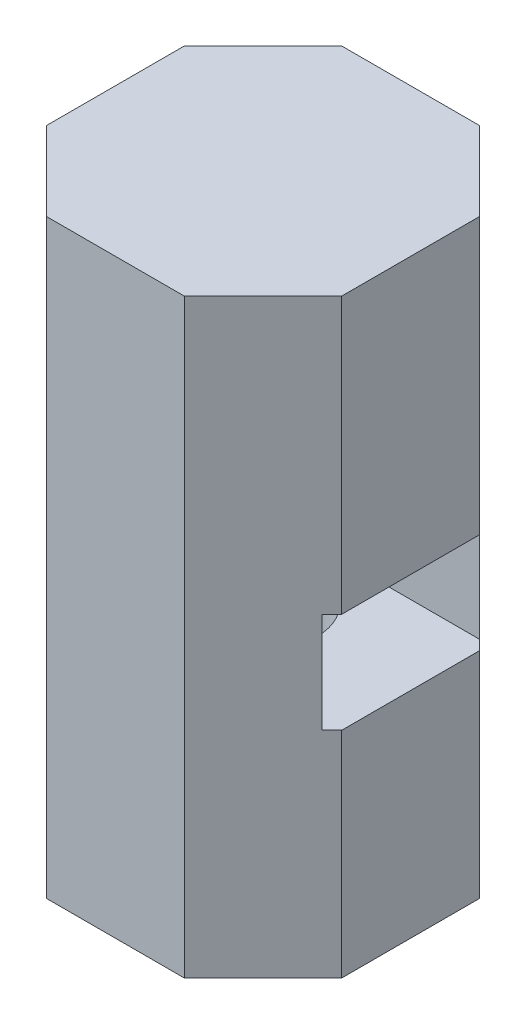
SolidWorks part; units mm, degrees
ref_plane "Front Plane" through (0, 0, 0) normal (0, 0, 1) x (1, 0, 0)
ref_plane "Top Plane" through (0, 0, 0) normal (0, 1, 0) x (1, 0, 0)
ref_plane "Right Plane" through (0, 0, 0) normal (1, 0, 0) x (0, 0, -1)
sketch "Sketch1" plane through (0, 0, 0) normal (0, 0, 1) x (1, 0, 0)
  line L1 (4, 0) -> (4, -30)
  line L2 (4, -30) -> (-11, -30)
  line L3 (-11, -30) -> (-11, 0)
  line L5 (-11, 0) -> (4, 0)
  line L10 (0, -55) -> (0, 55) construction
  line L11 (55, 0) -> (-55, 0) construction
  dimension "D4" = 15
  dimension "D5" = 30
  dimension "D7" = 4
extrude "Boss-Extrude1" add sketch "Sketch1" along normal mid plane 15
sketch "Sketch2" plane through (0, -30, 0) normal (0, -1, 0) x (1, 0, 0)
  line L0 (8.25, 0) -> (-8.25, 0) construction
  line L1 (-11, 7.5) -> (-11, -7.5) construction
  circle A0 centre (-3.5, 0) radius 5.25
  dimension "D1" = 10.5
  dimension "D2" = 7.5
extrude "Cut-Extrude1" cut sketch "Sketch2" against normal blind 6
sketch "Sketch4" plane through (0, -30, 0) normal (0, -1, 0) x (1, 0, 0)
  circle A0 centre (-3.5, 0) radius 2.75
  dimension "D1" = 5.5
extrude "Cut-Extrude3" cut sketch "Sketch4" against normal blind 28
sketch "Sketch5" plane through (4, 0, 0) normal (1, 0, 0) x (0, 0, -1)
  line L0 (0, 8.25) -> (0, -8.25) construction
  line L1 (-4, -14) -> (4, -14)
  line L2 (-4, -14) -> (-4, -19.1)
  line L3 (-4, -19.1) -> (4, -19.1)
  line L4 (4, -14) -> (4, -19.1)
  line L5 (8.25, 0) -> (-8.25, 0) construction
  dimension "D1" = 8
  dimension "D2" = 4
  dimension "D3" = 5.1
  dimension "D4" = 14
extrude "Cut-Extrude4" cut sketch "Sketch5" against normal up to next
chamfer "Chamfer3" distance 4 angle 45 4 edges at (-11, -15, 7.5) (-11, -15, -7.5) (4, -15, -7.5) (4, -15, 7.5)
